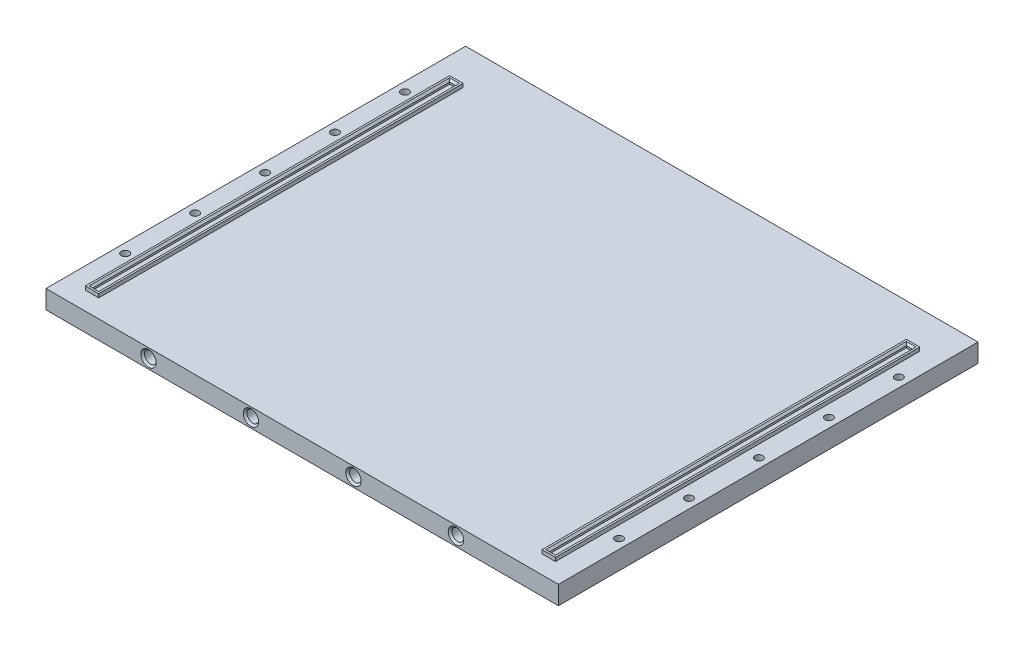
SolidWorks part; units mm, degrees
ref_plane "Спереди" through (0, 0, 0) normal (0, 0, 1) x (1, 0, 0)
ref_plane "Сверху" through (0, 0, 0) normal (0, 1, 0) x (1, 0, 0)
ref_plane "Справа" through (0, 0, 0) normal (1, 0, 0) x (0, 0, -1)
sketch "Эскиз1" plane through (0, 0, 0) normal (0, 1, 0) x (1, 0, 0)
  line L5 (-69, -56.5) -> (69, -56.5)
  line L6 (-69, -56.5) -> (-69, 56.5)
  line L7 (-69, 56.5) -> (69, 56.5)
  line L8 (69, -56.5) -> (69, 56.5)
  line L9 (-69, -56.5) -> (69, 56.5) construction
  line L10 (-69, 56.5) -> (69, -56.5) construction
  point P0 (0, 0)
  dimension "D1" = 113
  dimension "D2" = 138
extrude "Основание" add sketch "Эскиз1" along normal blind 5
sketch "Эскиз6" plane through (0, 0, 0) normal (0, -1, 0) x (1, 0, 0)
  line L0 (0, 45.5668) -> (0, -26.923) construction
  line L1 (-15.8226, 0) -> (3.0664, 0) construction
  line L2 (-37, 37) -> (0, 37) construction
  line L3 (-47, 47) -> (-27, 47)
  line L4 (-47, 47) -> (-47, 27)
  line L5 (-47, 27) -> (-27, 27)
  line L6 (-27, 47) -> (-27, 27)
  line L7 (-47, 47) -> (-27, 27) construction
  line L8 (-47, 27) -> (-27, 47) construction
  line L9 (-37, 37) -> (-37, 0) construction
  line L10 (47, 47) -> (27, 47)
  line L11 (47, 47) -> (47, 27)
  line L12 (47, 27) -> (27, 27)
  line L13 (27, 47) -> (27, 27)
  line L14 (27, -47) -> (27, -27)
  line L15 (47, -27) -> (27, -27)
  line L16 (47, -47) -> (47, -27)
  line L17 (47, -47) -> (27, -47)
  line L18 (-47, -47) -> (-27, -47)
  line L19 (-47, -47) -> (-47, -27)
  line L20 (-47, -27) -> (-27, -27)
  line L21 (-27, -47) -> (-27, -27)
  point P1 (-37, 37)
  dimension "D1" = 20
  dimension "D2" = 37
sketch "Эскиз2" plane through (0, 5, 0) normal (0, 1, 0) x (1, 0, 0)
  line L0 (0, 0) -> (0, -25.5598) construction
  line L1 (-61.5, 37.0772) -> (-61.5, 5.6487) construction
  line L2 (-21.6597, -2.55) -> (12.5108, -2.55) construction
  line L3 (-59.7, 46.5) -> (-63.3, 46.5)
  line L4 (-63.3, 46.5) -> (-63.3, -51.6)
  line L5 (-63.3, -2.55) -> (-62.3, -2.55)
  line L6 (-62.3, -50.6) -> (-62.3, 45.5)
  line L7 (-62.3, 45.5) -> (-60.7, 45.5)
  line L8 (-61.5, 45.5) -> (-61.5, 46.5)
  line L9 (-60.7, -50.6) -> (-60.7, 45.5)
  line L10 (-59.7, -2.55) -> (-60.7, -2.55)
  line L11 (-59.7, 46.5) -> (-59.7, -51.6)
  line L12 (-62.3, -50.6) -> (-60.7, -50.6)
  line L13 (-59.7, -51.6) -> (-63.3, -51.6)
  line L14 (-61.5, -50.6) -> (-61.5, -51.6)
  line L15 (61.5, -50.6) -> (61.5, -51.6)
  line L16 (59.7, -51.6) -> (63.3, -51.6)
  line L17 (62.3, -50.6) -> (60.7, -50.6)
  line L18 (59.7, 46.5) -> (59.7, -51.6)
  line L19 (59.7, -2.55) -> (60.7, -2.55)
  line L20 (60.7, -50.6) -> (60.7, 45.5)
  line L21 (61.5, 45.5) -> (61.5, 46.5)
  line L22 (62.3, 45.5) -> (60.7, 45.5)
  line L23 (62.3, -50.6) -> (62.3, 45.5)
  line L24 (63.3, -2.55) -> (62.3, -2.55)
  line L25 (63.3, 46.5) -> (63.3, -51.6)
  line L26 (59.7, 46.5) -> (63.3, 46.5)
  line L27 (-69, -56.5) -> (69, -56.5) construction
  dimension "D1" = 1
  dimension "D2" = 96.1
  dimension "D3" = 1.6
  dimension "D4" = 121.4
  dimension "D5" = 5.9
extrude "Ложемент материнской платы" add sketch "Эскиз2" along normal blind 1 contours L14 L12 L6 L5 L4 L13 | L7 L8 L3 L4 L5 L6 | L11 L3 L8 L7 L9 L10 | L12 L14 L13 L11 L10 L9 | L26 L21 L22 L23 L24 L25 | L26 L18 L19 L20 L22 L21 | L17 L20 L19 L18 L16 L15 | L25 L24 L23 L17 L15 L16 region at (-60.2144, 5, -22.3606) region at (-62.7856, 5, -22.3606) region at (-60.2144, 5, 27.4606) region at (-62.7856, 5, 27.4606) region at (62.7856, 5, 27.4606) region at (60.2144, 5, 27.4606) region at (62.7856, 5, -22.3606) region at (60.2144, 5, -22.3606)
fillet "Фаска первого ложемента" radius 0.5 4 edges at (-61.5, 6, -45.5) (-60.7, 6, 2.55) (-61.5, 6, 50.6) (-62.3, 6, 2.55) type face fillet profile chamfer first side face at (-61.5, 5.5, -45.5) first side face at (-61.5, 5.5, 50.6) first side face at (-60.7, 5.5, 2.55) first side face at (-62.3, 5.5, 2.55) second side face at (-61.5, 6, 2.55)
fillet "Фаска второго ложемента" radius 0.5 4 edges at (61.5, 6, 50.6) (60.7, 6, 2.55) (61.5, 6, -45.5) (62.3, 6, 2.55) type face fillet profile chamfer first side face at (61.5, 5.5, -45.5) first side face at (62.3, 5.5, 2.55) first side face at (60.7, 5.5, 2.55) first side face at (61.5, 5.5, 50.6) second side face at (61.5, 6, 2.55)
sketch "Эскиз3" plane through (0, 0, -56.5) normal (0, 0, -1) x (-1, 0, 0)
  line L0 (-69, 0) -> (69, 0) construction
  line L1 (-69, 5) -> (-69, 0) construction
  line L2 (-41.4, 2.5) -> (-69, 2.5) construction
  line L3 (41.4, 2.5) -> (69, 2.5) construction
  line L6 (69, 5) -> (69, 0) construction
  line L7 (-41.4, 2.5) -> (-13.8, 2.5) construction
  line L8 (-13.8, 2.5) -> (13.8, 2.5) construction
  line L9 (13.8, 2.5) -> (41.4, 2.5) construction
  circle A0 centre (-41.4, 2.5) radius 1.575
  circle A1 centre (-13.8, 2.5) radius 1.575
  circle A2 centre (13.8, 2.5) radius 1.575
  circle A3 centre (41.4, 2.5) radius 1.575
  dimension "D4" = 3.15
  dimension "D1" = 2.5
  dimension "D5" = 27.6
  dimension "D3" = 4
extrude "Крепежные отверсия передней и задней стенки" cut sketch "Эскиз3" against normal blind 4.2
ref_plane "Плоскость1" through (0, 0, 0) normal (0, 0, -1) x (-1, 0, 0)
mirror "Зеркальное отражение1" about plane through (0, 0, 0) normal (0, 0, -1) of "Крепежные отверсия передней и задней стенки"
sketch "Эскиз4" plane through (0, 0, 0) normal (0, -1, 0) x (1, 0, 0)
  line L0 (0, 34.8353) -> (0, -23.754) construction
  line L1 (-66.5, 56.5) -> (-66.5, 37.6667) construction
  line L2 (-69, 56.5) -> (69, 56.5) construction
  line L3 (-66.5, 37.6667) -> (-66.5, 18.8333) construction
  line L4 (-66.5, 18.8333) -> (-66.5, 0) construction
  line L5 (-66.5, 0) -> (-66.5, -18.8333) construction
  line L6 (-66.5, -18.8333) -> (-66.5, -37.6667) construction
  line L7 (-66.5, -37.6667) -> (-66.5, -56.5) construction
  line L8 (69, -56.5) -> (-69, -56.5) construction
  line L9 (-69, -56.5) -> (-69, 56.5) construction
  circle A0 centre (-66.5, 37.6667) radius 1.05
  circle A1 centre (-66.5, 18.8333) radius 1.05
  circle A2 centre (-66.5, 0) radius 1.05
  circle A3 centre (-66.5, -18.8333) radius 1.05
  circle A4 centre (-66.5, -37.6667) radius 1.05
  circle A5 centre (66.5, -37.6667) radius 1.05
  circle A6 centre (66.5, -18.8333) radius 1.05
  circle A7 centre (66.5, 0) radius 1.05
  circle A8 centre (66.5, 18.8333) radius 1.05
  circle A9 centre (66.5, 37.6667) radius 1.05
  dimension "D3" = 2.1
  dimension "D2" = 2.5
  dimension "D1" = 5
extrude "Отверстия крепежных винтов" cut sketch "Эскиз4" against normal up to next
sketch "Эскиз5" plane through (0, 0, 0) normal (0, -1, 0) x (1, 0, 0)
  line L0 (0, 88.0608) -> (0, 29.4715) construction
  line L1 (-66.5, 56.5) -> (-66.5, 37.6667) construction
  line L2 (-66.5, 37.6667) -> (-66.5, 18.8333) construction
  line L3 (-66.5, 18.8333) -> (-66.5, 0) construction
  line L4 (-66.5, 0) -> (-66.5, -18.8333) construction
  line L5 (-66.5, -18.8333) -> (-66.5, -37.6667) construction
  line L6 (-66.5, -37.6667) -> (-66.5, -56.5) construction
  line L7 (69, -56.5) -> (-69, -56.5) construction
  line L8 (-69, 56.5) -> (69, 56.5) construction
  circle A0 centre (-66.5, 37.6667) radius 2
  circle A1 centre (-66.5, 18.8333) radius 2
  circle A2 centre (-66.5, 0) radius 2
  circle A3 centre (-66.5, -18.8333) radius 2
  circle A4 centre (-66.5, -37.6667) radius 2
  circle A5 centre (66.5, -37.6667) radius 2
  circle A6 centre (66.5, -18.8333) radius 2
  circle A7 centre (66.5, 0) radius 2
  circle A8 centre (66.5, 18.8333) radius 2
  circle A9 centre (66.5, 37.6667) radius 2
  circle A10 centre (-66.5, -37.6667) radius 1.05 construction
  dimension "D1" = 4
extrude "Потай головок винтов" cut sketch "Эскиз5" against normal blind 3
chamfer "Фаска под запресовку" distance 0.5 angle 45 8 edges at (39.825, 2.5, 56.5) (12.225, 2.5, 56.5) (-15.375, 2.5, 56.5) (-42.975, 2.5, 56.5) (-42.975, 2.5, -56.5) (-15.375, 2.5, -56.5) (12.225, 2.5, -56.5) (39.825, 2.5, -56.5)
